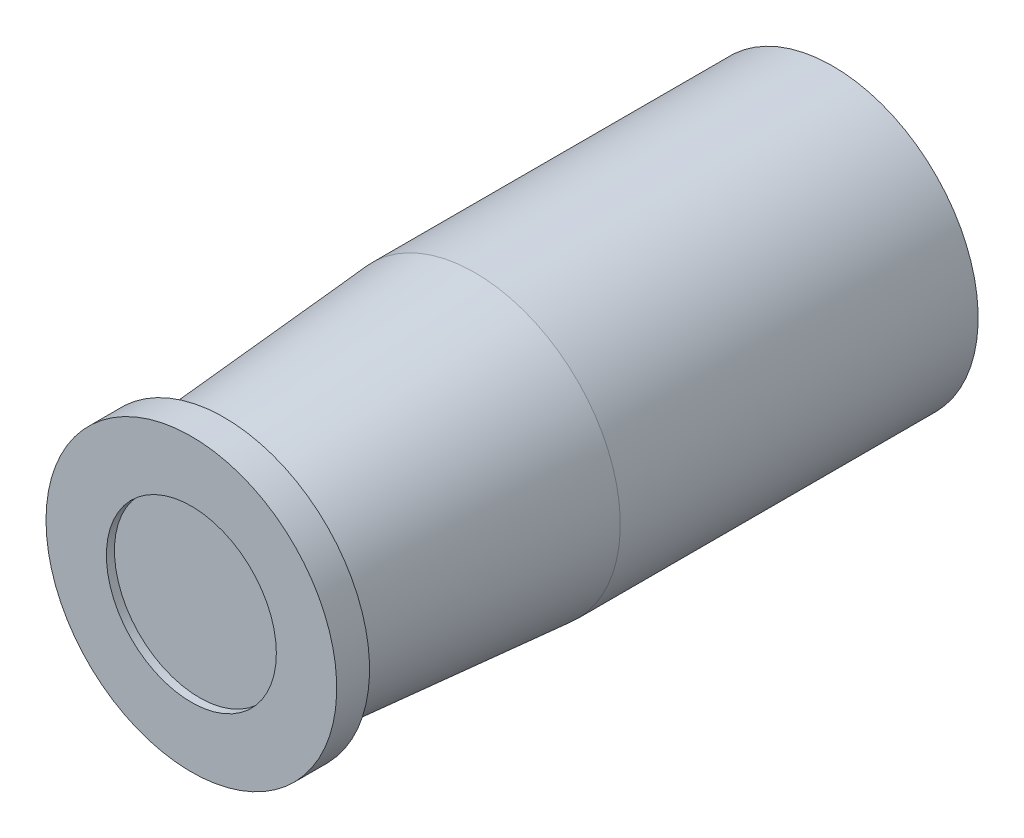
SolidWorks part; units mm, degrees
ref_plane "Front Plane" through (0, 0, 0) normal (0, 0, 1) x (1, 0, 0)
ref_plane "Top Plane" through (0, 0, 0) normal (0, 1, 0) x (1, 0, 0)
ref_plane "Right Plane" through (0, 0, 0) normal (1, 0, 0) x (0, 0, -1)
sketch "Sketch1" plane through (0, 0, 0) normal (0, 1, 0) x (1, 0, 0)
  line L0 (0, 0) -> (-4.875, 0)
  line L1 (-4.875, 0) -> (-4.875, 1.1)
  line L2 (-4.875, 1.1) -> (-4.215, 1.1)
  line L3 (-4.215, 1.1) -> (-4.875, 9.51)
  line L4 (-4.875, 9.51) -> (-4.875, 21.51)
  line L5 (-4.875, 21.51) -> (0, 21.51)
  line L6 (0, 21.51) -> (0, 0)
  point P6 (-4.126, 0.6705)
  dimension "D1" = 4.875
  dimension "D2" = 4.875
  dimension "D3" = 1.1
  dimension "D4" = 4.215
  dimension "D5" = 12
  dimension "D6" = 21.51
revolve "Revolve1" add sketch "Sketch1" angle 360 about L6
sketch "Sketch2" plane through (0, 0, 0) normal (0, 0, 1) x (1, 0, 0)
  circle A0 centre (0, 0) radius 2.85
  dimension "D1" = 5.7
extrude "Cut-Extrude1" cut sketch "Sketch2" against normal blind 0.27
